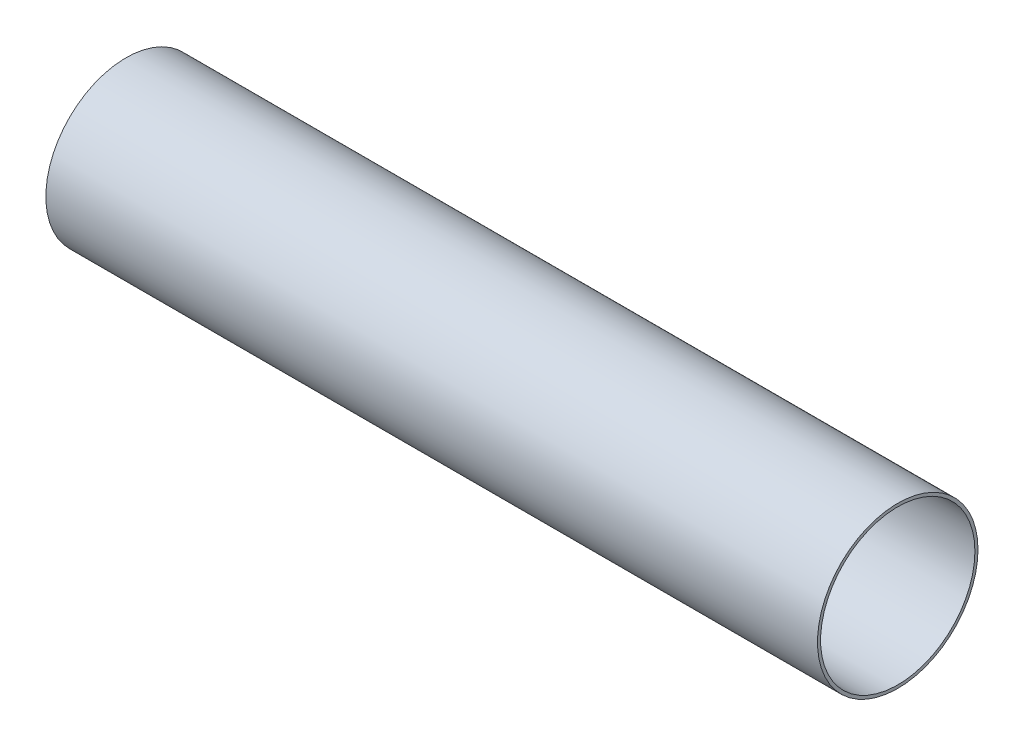
SolidWorks part; units mm, degrees
ref_plane "Front Plane" through (0, 0, 0) normal (1, 0, 0) x (0, 1, 0)
ref_plane "Top Plane" through (0, 0, 0) normal (0, 0, 1) x (0, 1, 0)
ref_plane "Right Plane" through (0, 0, 0) normal (0, 1, 0) x (-1, 0, 0)
sketch "Sketch1" plane through (0, 0, 0) normal (1, 0, 0) x (0, 1, 0)
  circle A0 centre (0, 0) radius 39.624
  circle A1 centre (0, 0) radius 38.1
  dimension "D1" = 79.248
  dimension "D2" = 76.2
extrude "Boss-Extrude1" add sketch "Sketch1" along normal blind 381
